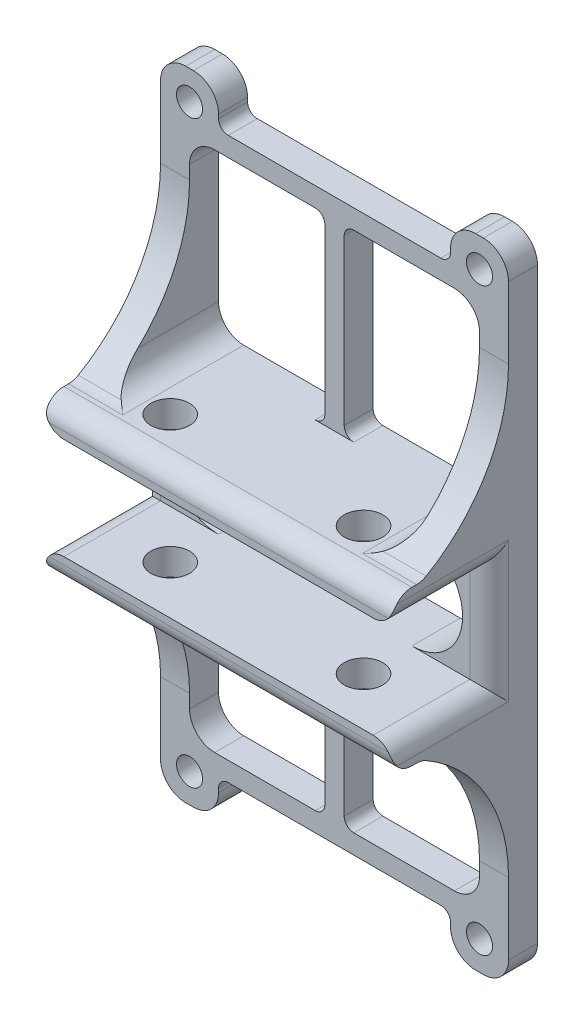
SolidWorks part; units mm, degrees
ref_plane "Front Plane" through (0, 0, 0) normal (0, 0, 1) x (1, 0, 0)
ref_plane "Top Plane" through (0, 0, 0) normal (0, 1, 0) x (1, 0, 0)
ref_plane "Right Plane" through (0, 0, 0) normal (1, 0, 0) x (0, 0, -1)
sketch "Sketch1" plane through (0, 0, 0) normal (0, 0, 1) x (1, 0, 0)
  line L0 (0, 22.146) -> (0, -22.6327) construction
  line L1 (8.8053, 0) -> (-7.3009, 0) construction
  line L4 (-18, 30.4) -> (-18, -30.4)
  line L6 (18, 30.4) -> (18, -30.4)
  line L8 (2, 27) -> (12.4, 27)
  line L9 (15, 24.4) -> (15, 10.6)
  line L10 (12.4, 8) -> (2, 8)
  line L11 (-15, 10.6) -> (-15, 24.4)
  line L14 (1, 26) -> (1, 9)
  line L15 (-12.4, 27) -> (-2, 27)
  line L16 (-1, 26) -> (-1, 9)
  line L17 (-15.4, 33) -> (-14.6, 33)
  line L18 (-12, 30.4) -> (-12, 30)
  line L19 (-11, 29) -> (11, 29)
  line L20 (12, 30) -> (12, 30.4)
  line L21 (14.6, 33) -> (15.4, 33)
  line L22 (-2, 8) -> (-12.4, 8)
  line L23 (-2, -8) -> (-12.4, -8)
  line L24 (14.6, -33) -> (15.4, -33)
  line L25 (12, -30) -> (12, -30.4)
  line L26 (-11, -29) -> (11, -29)
  line L27 (-12, -30.4) -> (-12, -30)
  line L28 (-15.4, -33) -> (-14.6, -33)
  line L29 (-1, -26) -> (-1, -9)
  line L30 (-12.4, -27) -> (-2, -27)
  line L31 (1, -26) -> (1, -9)
  line L32 (-15, -10.6) -> (-15, -24.4)
  line L33 (12.4, -8) -> (2, -8)
  line L34 (15, -24.4) -> (15, -10.6)
  line L35 (2, -27) -> (12.4, -27)
  circle A0 centre (-15, 30) radius 1.35
  circle A1 centre (15, 30) radius 1.35
  circle A2 centre (15, -30) radius 1.35
  circle A3 centre (-15, -30) radius 1.35
  arc A4 (12.4, 27) -> (15, 24.4) centre (12.4, 24.4) cw
  arc A5 (15, 10.6) -> (12.4, 8) centre (12.4, 10.6) cw
  arc A6 (-12.4, 8) -> (-15, 10.6) centre (-12.4, 10.6) cw
  arc A7 (-15, 24.4) -> (-12.4, 27) centre (-12.4, 24.4) cw
  arc A8 (-15.4, 33) -> (-18, 30.4) centre (-15.4, 30.4) ccw
  arc A9 (-14.6, 33) -> (-12, 30.4) centre (-14.6, 30.4) cw
  arc A10 (12, 30.4) -> (14.6, 33) centre (14.6, 30.4) cw
  arc A11 (15.4, 33) -> (18, 30.4) centre (15.4, 30.4) cw
  arc A12 (11, 29) -> (12, 30) centre (11, 30) ccw
  arc A13 (-2, 8) -> (-1, 9) centre (-2, 9) ccw
  arc A14 (2, 8) -> (1, 9) centre (2, 9) cw
  arc A15 (1, 26) -> (2, 27) centre (2, 26) cw
  arc A16 (-2, 27) -> (-1, 26) centre (-2, 26) cw
  arc A17 (-12, 30) -> (-11, 29) centre (-11, 30) ccw
  arc A18 (-12, -30) -> (-11, -29) centre (-11, -30) cw
  arc A19 (-2, -27) -> (-1, -26) centre (-2, -26) ccw
  arc A20 (1, -26) -> (2, -27) centre (2, -26) ccw
  arc A21 (2, -8) -> (1, -9) centre (2, -9) ccw
  arc A22 (-2, -8) -> (-1, -9) centre (-2, -9) cw
  arc A23 (11, -29) -> (12, -30) centre (11, -30) cw
  arc A24 (15.4, -33) -> (18, -30.4) centre (15.4, -30.4) ccw
  arc A25 (12, -30.4) -> (14.6, -33) centre (14.6, -30.4) ccw
  arc A26 (-14.6, -33) -> (-12, -30.4) centre (-14.6, -30.4) ccw
  arc A27 (-15.4, -33) -> (-18, -30.4) centre (-15.4, -30.4) cw
  arc A28 (-15, -24.4) -> (-12.4, -27) centre (-12.4, -24.4) ccw
  arc A29 (-12.4, -8) -> (-15, -10.6) centre (-12.4, -10.6) ccw
  arc A30 (15, -10.6) -> (12.4, -8) centre (12.4, -10.6) ccw
  arc A31 (12.4, -27) -> (15, -24.4) centre (12.4, -24.4) ccw
  circle A32 centre (15, -30) radius 1.35
  circle A33 centre (-15, -30) radius 1.35
  point P13 (0, 0)
  point P14 (0, 0)
  point P16 (-18, 0)
  point P103 (18, 0)
  dimension "D3" = 2.7
  dimension "D12" = 2.6
  dimension "D13" = 1
  dimension "D1" = 30
  dimension "D2" = 60
  dimension "D4" = 3
  dimension "D5" = 3
  dimension "D6" = 3
  dimension "D7" = 2
  dimension "D8" = 3
  dimension "D9" = 2
  dimension "D10" = 3
  dimension "D11" = 8
extrude "Boss-Extrude1" add sketch "Sketch1" along normal blind 15 contours A27 L28 A26 L27 A18 L26 A23 L25 A25 L24 A24 L6 A11 L21 A10 L20 A12 L19 A17 L18 A9 L17 A8 L4 A31 L35 A20 L31 A21 L33 A30 L34 A29 L23 A22 L29 A19 L30 A28 L32 A3 A2 A1 A0 region at (0, 0, 0)
sketch "Sketch2" plane through (18, 0, 0) normal (1, 0, 0) x (0, 0, -1)
  line L0 (-3, 33) -> (-3, 23)
  line L1 (-12, 8) -> (-15, 8)
  line L2 (-15, 8) -> (-15, 5.25)
  line L3 (-15, 5.25) -> (-5, 5.25)
  line L4 (-5, 5.25) -> (-5, -5.25)
  line L5 (-5, -5.25) -> (-15, -5.25)
  line L6 (-15, -5.25) -> (-15, -8)
  line L7 (-15, -8) -> (-12, -8)
  line L8 (-3, -23) -> (-3, -33)
  line L9 (6.3254, 0) -> (-25.9908, 0) construction
  line L10 (-15, 30.4) -> (-15, -30.4) construction
  line L11 (0, 30.4) -> (0, -30.4) construction
  line L12 (-15, 33) -> (0, 33) construction
  arc A0 (-12, -8) -> (-3, -23) centre (-20, -23) cw
  arc A1 (-3, 23) -> (-12, 8) centre (-20, 23) cw
  point P13 (-2.7026, 39.831)
  point P18 (0, 0)
  point P21 (0, 0)
  point P26 (-3, 8)
  point P27 (0, 0)
  point P28 (0, 0)
  point P29 (-10.3028, 10.6096)
  point P30 (-11.5048, 9.3427)
  point P31 (-7.697, 8)
  point P32 (-3, 27.4426)
  point P33 (-12.6831, 8)
  dimension "D7" = 10
  dimension "D1" = 10.5
  dimension "D2" = 10
  dimension "D3" = 3
  dimension "D4" = 3
  dimension "D5" = 3
  dimension "D6" = 8
extrude "Cut-Extrude2" cut sketch "Sketch2" against normal through all and the other way through all flip side to cut
fillet "Fillet2" radius 2 8 edges at (15.2, -8, 12) (0, -8, 12) (-15.2, -8, 12) (-15.2, 8, 12) (0, 8, 12) (15.2, 8, 12) (0, -8, 15) (0, 8, 15)
fillet "Fillet3" radius 2 6 edges at (-18, -5.25, 10) (-18, 0, 5) (-18, 5.25, 10) (18, 5.25, 10) (18, 0, 5) (18, -5.25, 10)
sketch "Sketch3" plane through (0, 0, 5) normal (0, 0, 1) x (1, 0, 0)
  line L0 (-10, 0) -> (10, 0) construction
  line L1 (-10, 5.25) -> (10, 5.25)
  line L2 (-10, -5.25) -> (10, -5.25)
  arc A0 (-10, 5.25) -> (-10, -5.25) centre (-10, 0) ccw
  arc A1 (10, -5.25) -> (10, 5.25) centre (10, 0) ccw
  point P3 (0, 0)
  dimension "D3" = 5.25
  dimension "D1" = 10
  dimension "D2" = 10
extrude "Cut-Extrude3" cut sketch "Sketch3" against normal blind 15
sketch "Sketch4" plane through (0, -8, 0) normal (0, -1, 0) x (1, 0, 0)
  line L0 (0, -4.3851) -> (0, 21.3551) construction
  line L1 (17.5612, 15) -> (-17.5612, 15) construction
  circle A0 centre (10, 10) radius 2
  circle A1 centre (-10, 10) radius 2
  dimension "D3" = 4
  dimension "D1" = 20
  dimension "D2" = 5
extrude "Cut-Extrude4" cut sketch "Sketch4" against normal through all
sketch "Sketch6" plane through (0, 0, 0) normal (1, 0, 0) x (0, 0, -1)
  line L0 (-3, 23) -> (-3, 30.4) construction
  line L3 (-17.6543, 8) -> (-3, 8)
  line L4 (-3, 24.6237) -> (-3, 8)
  line L5 (-13, 8) -> (-12.5167, 8) construction
  line L6 (-15.5296, -8) -> (-3, -8)
  line L7 (-3, -8) -> (-3, -39.0609)
  line L8 (-3, -30.4) -> (-3, -23) construction
  line L9 (-12.5167, -8) -> (-13, -8) construction
extrude "Cut-Extrude-Thin1" cut sketch "Sketch6" against normal up to next and the other way up to next thin thin type one direction wall 10
